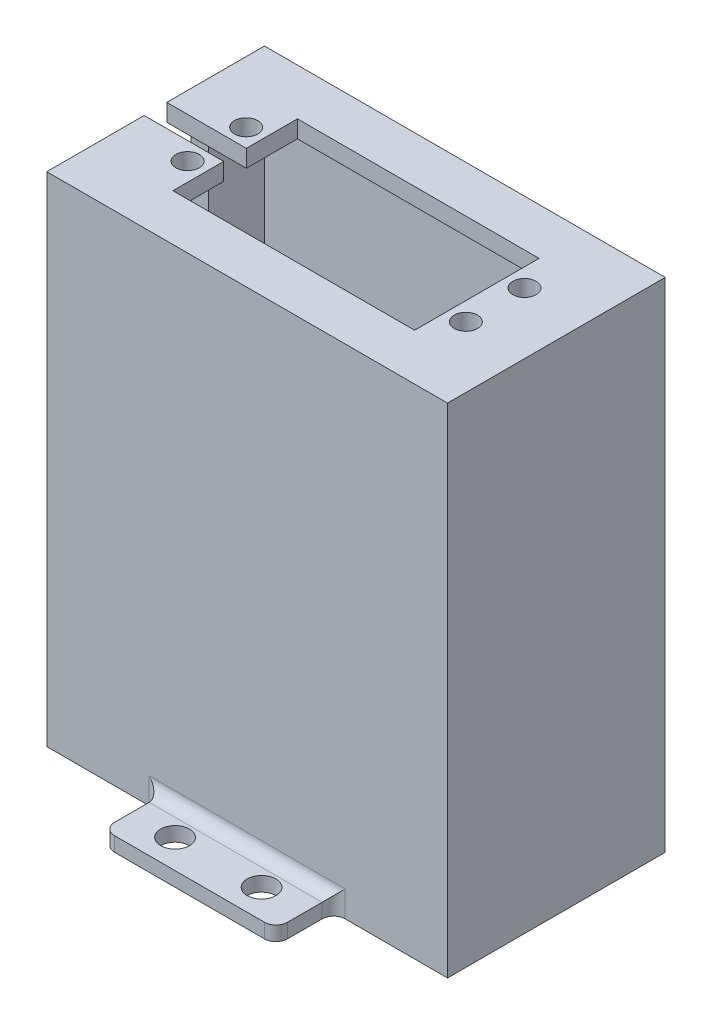
SolidWorks part; units mm, degrees
material "ABS"
ref_plane "Front Plane" through (0, 0, 0) normal (0, 0, 1) x (1, 0, 0)
ref_plane "Top Plane" through (0, 0, 0) normal (0, 1, 0) x (1, 0, 0)
ref_plane "Right Plane" through (0, 0, 0) normal (1, 0, 0) x (0, 0, -1)
sketch "Sketch1" plane through (0, 0, 0) normal (0, 1, 0) x (1, 0, 0)
  line L0 (-303.5027, 0) -> (303.5027, 0) construction
  line L1 (-223.52, -111.125) -> (223.52, -111.125)
  line L2 (-228.6, -106.045) -> (-228.6, 106.045)
  line L3 (-223.52, 111.125) -> (223.52, 111.125)
  line L4 (228.6, -106.045) -> (228.6, 106.045)
  line L5 (-228.6, -111.125) -> (228.6, 111.125) construction
  line L6 (-228.6, 111.125) -> (228.6, -111.125) construction
  line L7 (-303.5027, 36.5125) -> (303.5027, 36.5125) construction
  line L8 (-303.5027, -36.5125) -> (303.5027, -36.5125) construction
  line L9 (127, 111.125) -> (127, -111.125) construction
  line L10 (-142.24, 111.125) -> (-142.24, -111.125) construction
  arc A0 (223.52, 111.125) -> (228.6, 106.045) centre (223.52, 106.045) cw
  arc A1 (223.52, -111.125) -> (228.6, -106.045) centre (223.52, -106.045) ccw
  arc A2 (-223.52, -111.125) -> (-228.6, -106.045) centre (-223.52, -106.045) cw
  arc A3 (-228.6, 106.045) -> (-223.52, 111.125) centre (-223.52, 106.045) cw
  circle A4 centre (127, 36.5125) radius 2.54
  circle A5 centre (127, -36.5125) radius 2.54
  circle A6 centre (-142.24, 36.5125) radius 2.54
  circle A7 centre (-142.24, -36.5125) radius 2.54
  circle A8 centre (209.55, 0) radius 6.35
  point P0 (0, 0)
  point P20 (0, 0)
  point P37 (228.6, 0)
  dimension "D3" = 5.08
  dimension "D7" = 5.08
  dimension "D9" = 12.7
  dimension "D1" = 222.25
  dimension "D2" = 457.2
  dimension "D6" = 269.24
  dimension "D8" = 101.6
  dimension "D10" = 19.05
  dimension "D4" = 36.5125
  dimension "D5" = 36.5125
extrude "mainbaseplate" add sketch "Sketch1" along normal blind 3
sketch "Sketch2" plane through (0, 0, 0) normal (0, -1, 0) x (1, 0, 0)
  circle A0 centre (-142.24, 36.5125) radius 2.54 construction
  circle A1 centre (-142.24, -36.5125) radius 2.54 construction
  circle A2 centre (127, -36.5125) radius 2.54 construction
  circle A3 centre (127, 36.5125) radius 2.54 construction
  circle A4 centre (-142.24, 36.5125) radius 2.54
  circle A5 centre (-142.24, -36.5125) radius 2.54
  circle A6 centre (127, -36.5125) radius 2.54
  circle A7 centre (127, 36.5125) radius 2.54
  circle A8 centre (127, 36.5125) radius 6.096
  circle A9 centre (127, -36.5125) radius 6.096
  circle A10 centre (-142.24, -36.5125) radius 6.096
  circle A11 centre (-142.24, 36.5125) radius 6.096
  dimension "D1" = 12.192
extrude "BaseBoss-Extrude2" [suppressed] add sketch "Sketch2" along normal blind 10.16
sketch "Sketch3" plane through (0, 0, 0) normal (0, -1, 0) x (1, 0, 0)
  line L0 (-228.6, 0) -> (228.6, 0) construction
  line L1 (-228.6, -106.045) -> (-228.6, 106.045) construction
  line L2 (228.6, 106.045) -> (228.6, -106.045) construction
  line L3 (-228.6, 28.4) -> (-73.2, 28.4)
  line L4 (-228.6, -25.4) -> (-76.2, -25.4)
  line L6 (-228.6, 25.4) -> (-76.2, 25.4)
  line L7 (-76.2, -25.4) -> (-76.2, 25.4)
  line L8 (-228.6, -25.4) -> (-76.2, 25.4) construction
  line L9 (-228.6, 25.4) -> (-76.2, -25.4) construction
  line L10 (-73.2, -28.4) -> (-73.2, 28.4)
  line L11 (-228.6, -28.4) -> (-73.2, -28.4)
  line L12 (-228.6, 28.4) -> (-228.6, 25.4)
  line L13 (-228.6, -25.4) -> (-228.6, -28.4)
  point P6 (-152.4, 0)
  dimension "D1" = 50.8
  dimension "D2" = 152.4
  dimension "D3" = 76.2
  dimension "D4" = 3
extrude "Drive BatteryBoss-Extrude1" [suppressed] add sketch "Sketch3" along normal blind 28.575
sketch "Sketch4" [suppressed] plane through (0, -28.575, 0) normal (0, -1, 0) x (1, 0, 0)
  line L1 (-228.6, 28.4) -> (-73.2, 28.4)
  line L2 (-228.6, 28.4) -> (-228.6, -28.4)
  line L3 (-228.6, -28.4) -> (-73.2, -28.4)
  line L4 (-73.2, 28.4) -> (-73.2, -28.4)
extrude "drive Battery CapBoss-Extrude2" [suppressed] add sketch "Sketch4" along normal blind 3
sketch "Sketch5" [suppressed] plane through (0, -31.575, 0) normal (0, -1, 0) x (1, 0, 0)
  line L0 (-98.6, -28.4) -> (-73.2, -3)
  line L1 (-228.6, -28.4) -> (-73.2, -28.4) construction
  line L2 (-73.2, -28.4) -> (-73.2, 28.4) construction
  line L3 (-73.2, -3) -> (-52.1474, -3)
  line L4 (-52.1474, -3) -> (-52.1474, -43.6373)
  line L5 (-52.1474, -43.6373) -> (-98.6, -43.6373)
  line L6 (-98.6, -43.6373) -> (-98.6, -28.4)
  dimension "D1" = 25.4
  dimension "D2" = 25.4
  dimension "D3" = 21.0526
  dimension "D4" = 15.2373
extrude "Drive batterycutoutCut-Extrude1" [suppressed] cut sketch "Sketch5" against normal up to surface (31.575 mm away)
sketch "Sketch6" plane through (0, 3, 0) normal (0, 1, 0) x (1, 0, 0)
  line L0 (-228.6, 0) -> (228.6, 0) construction
  line L1 (-228.6, 106.045) -> (-228.6, -106.045) construction
  line L2 (228.6, -106.045) -> (228.6, 106.045) construction
  line L3 (-63.5, -41.1) -> (66.5, -41.1)
  line L4 (-63.5, -38.1) -> (63.5, -38.1)
  line L6 (-63.5, 38.1) -> (63.5, 38.1)
  line L7 (63.5, -38.1) -> (63.5, 38.1)
  line L8 (-63.5, -38.1) -> (63.5, 38.1) construction
  line L9 (-63.5, 38.1) -> (63.5, -38.1) construction
  line L10 (66.5, -41.1) -> (66.5, 41.1)
  line L11 (-63.5, 41.1) -> (66.5, 41.1)
  line L12 (-63.5, -41.1) -> (-63.5, -38.1)
  line L13 (-63.5, 38.1) -> (-63.5, 41.1)
  point P6 (0, 0)
  dimension "D1" = 127
  dimension "D2" = 76.2
  dimension "D4" = 63.5
  dimension "D3" = 3
extrude "PiBatteryBoxBoss-Extrude3" [suppressed] add sketch "Sketch6" along normal blind 25.4
sketch "Sketch7" [suppressed] plane through (0, 28.4, 0) normal (0, 1, 0) x (1, 0, 0)
  line L1 (66.5, 41.1) -> (-63.5, 41.1)
  line L2 (66.5, 41.1) -> (66.5, -41.1)
  line L3 (66.5, -41.1) -> (-63.5, -41.1)
  line L4 (-63.5, 41.1) -> (-63.5, -41.1)
extrude "PibatterytopBoss-Extrude4" [suppressed] add sketch "Sketch7" along normal blind 3
sketch "Sketch8" [suppressed] plane through (66.5, 0, 0) normal (1, 0, 0) x (0, 0, -1)
  line L0 (-38.1, 28.4) -> (38.1, 3) construction
  line L1 (38.1, 28.4) -> (-38.1, 28.4) construction
  line L2 (-31.75, 3) -> (31.75, 3)
  line L3 (-31.75, 3) -> (-31.75, 28.4)
  line L4 (-31.75, 28.4) -> (31.75, 28.4)
  line L5 (31.75, 3) -> (31.75, 28.4)
  line L6 (-31.75, 3) -> (31.75, 28.4) construction
  line L7 (-31.75, 28.4) -> (31.75, 3) construction
  point P2 (0, 15.7)
  dimension "D1" = 31.75
extrude "pibatterywiresCut-Extrude2" [suppressed] cut sketch "Sketch8" against normal blind 13.16
sketch "Sketch9" [suppressed] plane through (0, 31.4, 0) normal (0, 1, 0) x (1, 0, 0)
  line L0 (-63.5, 41.1) -> (66.5, -41.1) construction
  line L1 (-63.5, 0) -> (66.5, 0) construction
  line L2 (-5.08, -24.489) -> (52.92, -24.489) construction
  line L3 (-5.08, -24.489) -> (-5.08, 24.511) construction
  line L4 (-5.08, 24.511) -> (52.92, 24.511) construction
  line L5 (52.92, -24.489) -> (52.92, 24.511) construction
  line L6 (-5.08, -24.489) -> (52.92, 24.511) construction
  line L7 (-5.08, 24.511) -> (52.92, -24.489) construction
  line L8 (49.11, 20.701) -> (56.73, 20.701)
  line L9 (49.11, 20.701) -> (49.11, 28.321)
  line L10 (49.11, 28.321) -> (56.73, 28.321)
  line L11 (56.73, 20.701) -> (56.73, 28.321)
  line L12 (49.11, 20.701) -> (56.73, 28.321) construction
  line L13 (49.11, 28.321) -> (56.73, 20.701) construction
  line L14 (49.11, -28.299) -> (56.73, -28.299)
  line L16 (49.11, -20.679) -> (56.73, -20.679)
  line L18 (49.11, -28.299) -> (56.73, -20.679) construction
  line L19 (49.11, -20.679) -> (56.73, -28.299) construction
  line L20 (-8.89, 20.701) -> (-1.27, 20.701)
  line L21 (-8.89, 20.701) -> (-8.89, 28.321)
  line L22 (-8.89, 28.321) -> (-1.27, 28.321)
  line L23 (-1.27, 20.701) -> (-1.27, 28.321)
  line L24 (-8.89, 20.701) -> (-1.27, 28.321) construction
  line L25 (-8.89, 28.321) -> (-1.27, 20.701) construction
  line L26 (-8.89, -27.7078) -> (-1.27, -27.7078)
  line L27 (-8.89, -27.7078) -> (-8.89, -21.2702)
  line L28 (-8.89, -21.2702) -> (-1.27, -21.2702)
  line L29 (-1.27, -27.7078) -> (-1.27, -21.2702)
  line L30 (-8.89, -27.7078) -> (-1.27, -21.2702) construction
  line L31 (-8.89, -21.2702) -> (-1.27, -27.7078) construction
  line L32 (-63.5, 41.1) -> (-63.5, -41.1) construction
  line L33 (66.5, -41.1) -> (66.5, 41.1) construction
  line L34 (56.73, -20.679) -> (56.73, -28.299)
  line L35 (49.11, -20.679) -> (49.11, -28.299)
  circle A0 centre (52.92, 24.511) radius 1.35
  circle A1 centre (-5.08, 24.511) radius 1.35
  circle A2 centre (-5.08, -24.489) radius 1.35
  circle A3 centre (52.92, -24.489) radius 1.35
  point P4 (-8.057, 0)
  dimension "D3" = 2.7
  dimension "D4" = 7.62
  dimension "D1" = 58
  dimension "D2" = 49
  dimension "D5" = 7.62
  dimension "D6" = 7.62
  dimension "D7" = 7.62
  dimension "D8" = 7.62
  dimension "D9" = 7.62
  dimension "D10" = 58.42
  dimension "D11" = 24.511
  dimension "D12" = 7.62
extrude "PiBoardBoss-Extrude5" [suppressed] add sketch "Sketch9" along normal blind 3
sketch "Sketch10" plane through (0, 3, 0) normal (0, 1, 0) x (1, 0, 0)
  line L0 (228.6, 0) -> (-228.6, 0) construction
  line L1 (228.6, -106.045) -> (228.6, 106.045) construction
  line L2 (-228.6, 106.045) -> (-228.6, -106.045) construction
  line L3 (104.95, 18.875) -> (174.45, 18.875)
  line L4 (107.95, -15.875) -> (171.45, -15.875)
  line L5 (107.95, -15.875) -> (107.95, -6.175)
  line L6 (107.95, 15.875) -> (171.45, 15.875)
  line L7 (171.45, -15.875) -> (171.45, 15.875)
  line L8 (107.95, -15.875) -> (171.45, 15.875) construction
  line L9 (107.95, 15.875) -> (171.45, -15.875) construction
  line L10 (174.45, -18.875) -> (174.45, 18.875)
  line L11 (104.95, -18.875) -> (174.45, -18.875)
  line L12 (104.95, -18.875) -> (104.95, -6.175)
  line L13 (104.95, 6.175) -> (107.95, 6.175)
  line L14 (104.95, -6.175) -> (107.95, -6.175)
  line L15 (104.95, 6.175) -> (104.95, 18.875)
  line L16 (104.95, -18.875) -> (104.95, 18.875) construction
  line L17 (107.95, 6.175) -> (107.95, 15.875)
  line L18 (107.95, -15.875) -> (107.95, 15.875) construction
  point P6 (139.7, 0)
  dimension "D1" = 31.75
  dimension "D2" = 63.5
  dimension "D3" = 139.7
  dimension "D5" = 12.7
  dimension "D6" = 12.7
  dimension "D4" = 3
extrude "PanTilt-Extrude6" add sketch "Sketch10" along normal blind 83.34
sketch "Sketch11" plane through (0, 86.34, 0) normal (0, 1, 0) x (1, 0, 0)
  line L1 (104.95, 18.875) -> (174.45, 18.875)
  line L2 (104.95, 18.875) -> (104.95, -18.875)
  line L3 (104.95, -18.875) -> (174.45, -18.875)
  line L4 (174.45, 18.875) -> (174.45, -18.875)
extrude "Boss-Extrude7" add sketch "Sketch11" along normal blind 3
sketch "Sketch12" plane through (0, 89.34, 0) normal (0, 1, 0) x (1, 0, 0)
  line L0 (104.95, 0) -> (174.45, 0) construction
  line L1 (104.95, 18.875) -> (104.95, -18.875) construction
  line L2 (174.45, -18.875) -> (174.45, 18.875) construction
  line L3 (118.745, 1.9377) -> (104.95, 1.9377)
  line L4 (118.745, -10.795) -> (160.655, -10.795)
  line L5 (118.745, -10.795) -> (118.745, -1.9901)
  line L6 (118.745, 10.795) -> (160.655, 10.795)
  line L7 (160.655, -10.795) -> (160.655, 10.795)
  line L8 (118.745, -10.795) -> (160.655, 10.795) construction
  line L9 (118.745, 10.795) -> (160.655, -10.795) construction
  line L10 (115.57, -5.08) -> (163.83, -5.08) construction
  line L11 (115.57, -5.08) -> (115.57, 5.08) construction
  line L12 (115.57, 5.08) -> (163.83, 5.08) construction
  line L13 (163.83, -5.08) -> (163.83, 5.08) construction
  line L14 (115.57, -5.08) -> (163.83, 5.08) construction
  line L15 (115.57, 5.08) -> (163.83, -5.08) construction
  line L16 (118.745, -1.9901) -> (104.95, -1.9901)
  line L17 (118.745, 1.9377) -> (118.745, 10.795)
  line L18 (104.95, 1.9377) -> (95.8416, 0)
  line L19 (95.8416, 0) -> (104.95, -1.9901)
  circle A0 centre (163.83, 5.08) radius 2.0193
  circle A1 centre (163.83, -5.08) radius 2.0193
  circle A2 centre (115.57, 5.08) radius 2.0193
  circle A3 centre (115.57, -5.08) radius 2.0193
  point P6 (139.7, 0)
  point P11 (139.7, 0)
  dimension "D5" = 4.0386
  dimension "D1" = 21.59
  dimension "D2" = 41.91
  dimension "D3" = 48.26
  dimension "D4" = 10.16
  dimension "D6" = 1.9377
  dimension "D7" = 1.9901
extrude "Cut-Extrude3" cut sketch "Sketch12" against normal up to surface (86.34 mm away) up to face at (209.55, 3, 6.35)
sketch "Sketch13" plane through (0, 3, 0) normal (0, 1, 0) x (1, 0, 0)
  line L0 (228.6, 0) -> (-228.6, 0) construction
  line L1 (228.6, -106.045) -> (228.6, 106.045) construction
  line L2 (-228.6, 106.045) -> (-228.6, -106.045) construction
  line L3 (198.12, 0) -> (198.12, 25.4)
  line L4 (198.12, 25.4) -> (172.72, 69.3941)
  line L5 (172.72, 69.3941) -> (136.799, 105.3151)
  line L6 (198.12, 25.4) -> (198.12, 129.9736) construction
  line L7 (172.72, 69.3941) -> (172.72, 97.5573) construction
  line L8 (136.799, 105.3151) -> (-185.781, 105.3151)
  line L9 (-185.781, 105.3151) -> (-221.702, 69.3941)
  line L10 (-221.702, 69.3941) -> (-221.702, 0)
  line L11 (-185.781, 105.3151) -> (-290.6809, 105.3151) construction
  line L12 (195.12, 0) -> (195.12, 24.5962)
  line L13 (195.12, 24.5962) -> (170.3194, 67.552)
  line L14 (170.3194, 67.552) -> (135.5563, 102.3151)
  line L15 (135.5563, 102.3151) -> (-184.5384, 102.3151)
  line L16 (-184.5384, 102.3151) -> (-218.702, 68.1514)
  line L17 (-218.702, 68.1514) -> (-218.702, 0)
  line L18 (172.72, -69.3941) -> (172.72, -97.5573) construction
  line L19 (198.12, -25.4) -> (198.12, -129.9736) construction
  line L20 (-218.702, -68.1514) -> (-218.702, 0)
  line L21 (-184.5384, -102.3151) -> (-218.702, -68.1514)
  line L22 (135.5563, -102.3151) -> (-184.5384, -102.3151)
  line L23 (170.3194, -67.552) -> (135.5563, -102.3151)
  line L24 (195.12, -24.5962) -> (170.3194, -67.552)
  line L25 (195.12, 0) -> (195.12, -24.5962)
  line L26 (-221.702, -69.3941) -> (-221.702, 0)
  line L27 (-185.781, -105.3151) -> (-221.702, -69.3941)
  line L28 (136.799, -105.3151) -> (-185.781, -105.3151)
  line L29 (172.72, -69.3941) -> (136.799, -105.3151)
  line L30 (198.12, -25.4) -> (172.72, -69.3941)
  line L31 (198.12, 0) -> (198.12, -25.4)
  dimension "D1" = 30.48
  dimension "D2" = 25.4
  dimension "D3" = 30
  dimension "D4" = 50.8
  dimension "D5" = 45
  dimension "D6" = 50.8
  dimension "D7" = 322.58
  dimension "D8" = 50.8
  dimension "D9" = 45
  dimension "D10" = 3
extrude "Bottom Shell WallsBoss-Extrude8" [suppressed] add sketch "Sketch13" along normal blind 68.58
sketch "Sketch14" [suppressed] plane through (121.057, 0, -121.057) normal (0.7071, 0, -0.7071) x (-0.7071, 0, -0.7071)
  line L0 (-47.6625, 71.58) -> (-47.6625, 3) construction
  line L1 (-73.0625, 71.58) -> (-22.2625, 71.58) construction
  line L2 (-73.0625, 3) -> (-22.2625, 3) construction
  line L3 (-47.6625, 37.29) -> (-25.0131, 37.29) construction
  circle A0 centre (-47.6625, 64.722) radius 1.3526
  circle A1 centre (-47.6625, 9.858) radius 1.3526
  circle A2 centre (-29.8825, 37.29) radius 4.7625
  point P10 (-47.6625, 37.29)
  dimension "D1" = 2.7051
  dimension "D4" = 9.525
  dimension "D2" = 54.864
  dimension "D3" = 27.432
  dimension "D5" = 17.78
extrude "Sharp1Cut-Extrude4" [suppressed] cut sketch "Sketch14" against normal blind 12.7
sketch "Sketch15" [suppressed] plane through (159.5885, 0, -92.1385) normal (0.866, 0, -0.5) x (-0.5, 0, -0.866)
  line L0 (-51.663, 71.58) -> (-51.663, 3) construction
  line L1 (-77.063, 71.58) -> (-26.263, 71.58) construction
  line L2 (-77.063, 3) -> (-26.263, 3) construction
  line L3 (-51.663, 37.29) -> (-29.7061, 37.29) construction
  circle A0 centre (-51.663, 64.722) radius 1.3526
  circle A1 centre (-51.663, 9.858) radius 1.3526
  circle A2 centre (-33.883, 37.29) radius 4.7625
  point P10 (-51.663, 37.29)
  dimension "D1" = 2.7051
  dimension "D4" = 9.525
  dimension "D2" = 27.432
  dimension "D3" = 54.864
  dimension "D5" = 17.78
extrude "Sharp2Cut-Extrude5" [suppressed] cut sketch "Sketch15" against normal blind 7.62
sketch "Sketch16" [suppressed] plane through (198.12, 0, 0) normal (1, 0, 0) x (0, 0, -1)
  line L0 (0, 71.58) -> (0, 3) construction
  line L1 (-25.4, 71.58) -> (25.4, 71.58) construction
  line L2 (-25.4, 3) -> (25.4, 3) construction
  line L3 (0, 37.29) -> (21.2381, 37.29) construction
  circle A0 centre (0, 64.722) radius 1.3526
  circle A1 centre (0, 9.858) radius 1.3525
  circle A2 centre (17.78, 37.29) radius 4.7625
  dimension "D1" = 2.7051
  dimension "D4" = 9.525
  dimension "D2" = 27.432
  dimension "D3" = 54.864
  dimension "D5" = 17.78
extrude "Sharp3Cut-Extrude6" [suppressed] cut sketch "Sketch16" against normal blind 7.62
sketch "Sketch17" [suppressed] plane through (159.5885, 0, 92.1385) normal (0.866, 0, 0.5) x (0.5, 0, -0.866)
  line L0 (51.663, 71.58) -> (51.663, 3) construction
  line L1 (26.263, 71.58) -> (77.063, 71.58) construction
  line L2 (26.263, 3) -> (77.063, 3) construction
  line L3 (51.663, 37.29) -> (70.4023, 37.29) construction
  circle A0 centre (51.663, 64.722) radius 1.3526
  circle A1 centre (51.663, 9.858) radius 1.3526
  circle A2 centre (69.443, 37.29) radius 4.7625
  dimension "D1" = 2.7051
  dimension "D2" = 2.7051
  dimension "D3" = 9.525
  dimension "D4" = 17.78
  dimension "D5" = 27.432
  dimension "D6" = 54.864
extrude "SharpCut-Extrude7" [suppressed] cut sketch "Sketch17" against normal blind 7.62
sketch "Sketch18" [suppressed] plane through (121.057, 0, 121.057) normal (0.7071, 0, 0.7071) x (0.7071, 0, -0.7071)
  line L0 (47.6625, 71.58) -> (47.6625, 3) construction
  line L1 (22.2625, 71.58) -> (73.0625, 71.58) construction
  line L2 (22.2625, 3) -> (73.0625, 3) construction
  line L3 (25.604, 37.29) -> (69.7209, 37.29) construction
  circle A0 centre (47.6625, 64.722) radius 1.3526
  circle A1 centre (47.6625, 9.858) radius 1.3526
  circle A2 centre (65.4425, 37.29) radius 4.7625
  point P13 (47.6625, 37.29)
  dimension "D1" = 9.525
  dimension "D3" = 2.7051
  dimension "D4" = 2.7051
  dimension "D2" = 17.78
  dimension "D5" = 27.432
  dimension "D6" = 54.864
extrude "SharpCut-Extrude8" [suppressed] cut sketch "Sketch18" against normal blind 7.62
sketch "Sketch19" [suppressed] plane through (0, 71.58, 0) normal (0, 1, 0) x (1, 0, 0)
  line L0 (-223.52, -111.125) -> (223.52, -111.125) construction
  line L1 (228.6, -106.045) -> (228.6, 106.045) construction
  line L2 (223.52, 111.125) -> (-223.52, 111.125) construction
  line L3 (104.95, -111.125) -> (223.52, -111.125)
  line L4 (228.6, -106.045) -> (228.6, 106.045)
  line L5 (223.52, 111.125) -> (104.95, 111.125)
  line L6 (104.95, 111.125) -> (104.95, -111.125)
  arc A0 (223.52, -111.125) -> (228.6, -106.045) centre (223.52, -106.045) ccw construction
  arc A1 (228.6, 106.045) -> (223.52, 111.125) centre (223.52, 106.045) ccw construction
  arc A2 (223.52, -111.125) -> (228.6, -106.045) centre (223.52, -106.045) ccw
  arc A3 (228.6, 106.045) -> (223.52, 111.125) centre (223.52, 106.045) ccw
extrude "TopSensorplateBoss-Extrude8" [suppressed] add sketch "Sketch19" along normal blind 3
sketch "Sketch21" [suppressed] plane through (0, 74.58, 0) normal (0, 1, 0) x (1, 0, 0)
  line L0 (104.95, -18.875) -> (174.45, -18.875) construction
  line L1 (174.45, -18.875) -> (174.45, 18.875) construction
  line L2 (174.45, 18.875) -> (104.95, 18.875) construction
  line L3 (104.95, -18.875) -> (164.29, -18.875)
  line L4 (174.45, -8.715) -> (174.45, 8.715)
  line L5 (164.29, 18.875) -> (104.95, 18.875)
  line L6 (104.95, 18.875) -> (84.8462, 2.2825)
  line L7 (84.8462, 2.2825) -> (104.95, -18.875)
  arc A0 (164.29, -18.875) -> (174.45, -8.715) centre (164.29, -8.715) ccw
  arc A1 (174.45, 8.715) -> (164.29, 18.875) centre (164.29, 8.715) ccw
  circle A2 centre (127, -36.5125) radius 6.096 construction
  circle A3 centre (127, 36.5125) radius 6.096 construction
  circle A4 centre (127, -36.5125) radius 6.096
  circle A5 centre (127, 36.5125) radius 6.096
  dimension "D1" = 10.16
extrude "topsensorplateCut-Extrude4" [suppressed] cut sketch "Sketch21" against normal blind 8.08
sketch "Sketch22" [suppressed] plane through (0, 0, 0) normal (0, -1, 0) x (1, 0, 0)
  line L0 (228.6, 0) -> (-228.6, 0) construction
  line L1 (228.6, 106.045) -> (228.6, -106.045) construction
  line L2 (-228.6, 28.4) -> (-228.6, -28.4) construction
  line L3 (220.98, 0) -> (220.98, 76.2)
  line L4 (220.98, 76.2) -> (193.675, 103.505)
  line L5 (193.675, 103.505) -> (-25.4, 103.505)
  line L6 (-223.52, 111.125) -> (223.52, 111.125) construction
  line L7 (217.98, 0) -> (217.98, 74.9574)
  line L8 (217.98, 74.9574) -> (192.4324, 100.505)
  line L9 (192.4324, 100.505) -> (-25.4, 100.505)
  line L10 (-25.4, 103.505) -> (-25.4, 100.505)
  line L11 (217.98, 0) -> (217.98, -74.9574)
  line L12 (220.98, 0) -> (220.98, -76.2)
  line L13 (-25.4, -103.505) -> (-25.4, -100.505)
  line L14 (192.4324, -100.505) -> (-25.4, -100.505)
  line L15 (217.98, -74.9574) -> (192.4324, -100.505)
  line L16 (193.675, -103.505) -> (-25.4, -103.505)
  line L17 (220.98, -76.2) -> (193.675, -103.505)
  line L18 (-220.98, 28.4) -> (-220.98, 76.2)
  line L19 (-73.2, 28.4) -> (-228.6, 28.4) construction
  line L20 (-220.98, 76.2) -> (-193.548, 103.505)
  line L21 (-193.548, 103.505) -> (-127, 103.505)
  line L22 (-228.6, 28.4) -> (-228.6, 106.045) construction
  line L23 (-217.98, 28.4) -> (-217.98, 74.9533)
  line L24 (-217.98, 74.9533) -> (-192.3094, 100.505)
  line L25 (-192.3094, 100.505) -> (-127, 100.505)
  line L26 (-127, 103.505) -> (-127, 100.505)
  line L27 (-220.98, 28.4) -> (-217.98, 28.4)
  line L28 (-127, -103.505) -> (-127, -100.505)
  line L29 (-192.3094, -100.505) -> (-127, -100.505)
  line L30 (-217.98, -74.9533) -> (-192.3094, -100.505)
  line L31 (-217.98, -28.4) -> (-217.98, -74.9533)
  line L32 (-193.548, -103.505) -> (-127, -103.505)
  line L33 (-220.98, -76.2) -> (-193.548, -103.505)
  line L34 (-220.98, -28.4) -> (-220.98, -76.2)
  line L35 (-220.98, -28.4) -> (-217.98, -28.4)
  dimension "D1" = 7.62
  dimension "D2" = 7.62
  dimension "D3" = 76.2
  dimension "D4" = 34.925
  dimension "D5" = 254
  dimension "D7" = 7.62
  dimension "D8" = 76.2
  dimension "D9" = 7.62
  dimension "D10" = 101.6
  dimension "D11" = 35.052
  dimension "D6" = 3
  dimension "D12" = 3
extrude "frontrockerpanBoss-Extrude9" [suppressed] add sketch "Sketch22" along normal blind 45.72
sketch "Sketch23" [suppressed] plane through (0, 0, -103.505) normal (0, 0, -1) x (-1, 0, 0)
  line L0 (25.4, 0) -> (-193.675, 0) construction
  line L2 (-223.1134, -81.0052) -> (22.7571, -81.0052) construction
  line L3 (22.7571, -81.0052) -> (254.0819, -81.0052) construction
  circle A1 centre (-127, -81.0052) radius 63.5
  circle A2 centre (152.4, -81.0052) radius 63.5
  dimension "D1" = 81.0052
  dimension "D4" = 127
  dimension "D2" = 22.7571
  dimension "D3" = 223.1134
  dimension "D5" = 127
  dimension "D6" = 279.4
extrude "TireCut-Extrude5" [suppressed] cut sketch "Sketch23" against normal blind 25.4
sketch "Sketch24" [suppressed] plane through (-221.702, 0, 0) normal (-1, 0, 0) x (0, 0, 1)
  line L0 (-69.3941, 71.58) -> (69.3941, 3) construction
  circle A0 centre (0, 37.29) radius 10.9855
  dimension "D1" = 21.971
extrude "Cut-Extrude6" [suppressed] cut sketch "Sketch24" against normal blind 7.62
sketch "Sketch25" [suppressed] plane through (0, 71.58, 0) normal (0, 1, 0) x (1, 0, 0)
  line L3 (-223.52, -111.125) -> (223.52, -111.125) construction
  line L5 (-228.6, 106.045) -> (-228.6, -106.045) construction
  line L6 (223.52, 111.125) -> (-223.52, 111.125) construction
  line L7 (-223.52, -111.125) -> (-147.32, -111.125)
  line L8 (-228.6, 106.045) -> (-228.6, -106.045)
  line L9 (-147.32, 111.125) -> (-223.52, 111.125)
  line L10 (-147.32, 111.125) -> (-147.32, -111.125)
  arc A2 (-228.6, -106.045) -> (-223.52, -111.125) centre (-223.52, -106.045) ccw construction
  arc A3 (-223.52, 111.125) -> (-228.6, 106.045) centre (-223.52, 106.045) ccw construction
  arc A4 (-228.6, -106.045) -> (-223.52, -111.125) centre (-223.52, -106.045) ccw
  arc A5 (-223.52, 111.125) -> (-228.6, 106.045) centre (-223.52, 106.045) ccw
  dimension "D1" = 147.32
extrude "ReartopdeckBoss-Extrude10" [suppressed] add sketch "Sketch25" along normal blind 3
sketch "Sketch28" [suppressed] plane through (0, 0, 103.505) normal (0, 0, 1) x (1, 0, 0)
  line L0 (-205.194, -45.72) -> (-93.1399, -108.4782)
  line L1 (-93.1399, -108.4782) -> (179.794, -45.72)
  line L2 (74.206, -45.72) -> (-102.0458, -69.7467)
  line L3 (-102.0458, -69.7467) -> (-127, -22.8065)
  arc A0 (-192.3094, -31.6141) -> (-205.194, -45.72) centre (-152.4, -81.0052) ccw construction
  arc A1 (-127, -22.8065) -> (-192.3094, -31.6141) centre (-152.4, -81.0052) ccw construction
  arc A2 (179.794, -45.72) -> (74.206, -45.72) centre (127, -81.0052) ccw construction
  arc A3 (-192.3094, -31.6141) -> (-205.194, -45.72) centre (-152.4, -81.0052) ccw
  arc A4 (-127, -22.8065) -> (-192.3094, -31.6141) centre (-152.4, -81.0052) ccw
  arc A5 (179.794, -45.72) -> (74.206, -45.72) centre (127, -81.0052) ccw
extrude "TireCut-Extrude8" [suppressed] cut sketch "Sketch28" against normal blind 35.56
sketch "Sketch30" [suppressed] plane through (0, 74.58, 0) normal (0, 1, 0) x (1, 0, 0)
  line L0 (-147.32, 0) -> (-228.6, 0) construction
  line L1 (-147.32, -111.125) -> (-147.32, 111.125) construction
  line L2 (-228.6, 106.045) -> (-228.6, -106.045) construction
  circle A0 centre (-166.37, 0) radius 6.35
  dimension "D1" = 12.7
  dimension "D2" = 19.05
extrude "Cut-Extrude10" [suppressed] cut sketch "Sketch30" against normal blind 11.684
sketch "Sketch31" [suppressed] plane through (0, 0, 0) normal (1, 0, 0) x (0, 0, -1)
  line L0 (102.3151, 71.58) -> (102.3151, 3) construction
  line L1 (-102.3151, 71.58) -> (-76.9151, 71.58)
  line L2 (-102.3151, 71.58) -> (-102.3151, 68.58)
  line L3 (-102.3151, 68.58) -> (-76.9151, 68.58)
  line L4 (102.3151, 71.58) -> (102.3151, 68.58)
  line L5 (-76.9151, 71.58) -> (-76.9151, 68.58)
  line L6 (76.9151, 71.58) -> (76.9151, 68.58)
  line L7 (76.9151, 71.58) -> (102.3151, 71.58)
  line L8 (76.9151, 68.58) -> (102.3151, 68.58)
  dimension "D1" = 3
  dimension "D2" = 25.4
  dimension "D3" = 25.4
extrude "Boss-Extrude8" [suppressed] add sketch "Sketch31" along normal blind 134.62 and the other way blind 180.34
sketch "Sketch32" plane through (0, 0, 0) normal (0, -1, 0) x (1, 0, 0)
  line L1 (-362.1056, 298.8668) -> (350.2899, 298.8668)
  line L2 (-362.1056, 298.8668) -> (-362.1056, -225.3293)
  line L3 (-362.1056, -225.3293) -> (350.2899, -225.3293)
  line L4 (350.2899, 298.8668) -> (350.2899, -225.3293)
extrude "Cut-Extrude11" cut sketch "Sketch32" against normal up to surface (3 mm away) up to face at (209.55, 3, 6.35)
sketch "Sketch33" plane through (0, 3, 0) normal (0, -1, 0) x (1, 0, 0)
  line L0 (174.45, 0) -> (90.833, 0) construction
  line L1 (154.7, 28.875) -> (124.7, 28.875)
  line L2 (154.7, 28.875) -> (154.7, -28.875)
  line L3 (154.7, -28.875) -> (124.7, -28.875)
  line L4 (124.7, 28.875) -> (124.7, -28.875)
  line L5 (174.45, 18.875) -> (174.45, -18.875) construction
  line L6 (104.95, 18.875) -> (174.45, 18.875) construction
  line L7 (174.45, -18.875) -> (104.95, -18.875) construction
  line L8 (139.7, -18.875) -> (139.7, 50.2921) construction
  line L9 (147.2, 28.875) -> (147.2, 18.875) construction
  line L10 (154.7, -18.875) -> (124.7, -18.875)
  line L11 (154.7, 18.875) -> (124.7, 18.875)
  circle A0 centre (147.2, 23.875) radius 2.5
  circle A1 centre (132.2, 23.875) radius 2.5
  circle A2 centre (132.2, -23.875) radius 2.5
  circle A3 centre (147.2, -23.875) radius 2.5
  point P9 (139.7, 28.875)
  point P14 (139.7, -28.875)
  point P16 (154.7, 0)
  point P22 (147.2, 23.875)
  line M13 (104.95, -18.875) -> (174.45, -18.875)
  line M15 (174.45, 18.875) -> (104.95, 18.875)
  dimension "D3" = 5
  dimension "D4" = 7.5
  dimension "D1" = 10
  dimension "D2" = 30
extrude "Boss-Extrude9" add sketch "Sketch33" against normal blind 2.5 contours L1 L4 L2 A0 A1 M15 | L4 L3 L2 A2 A3 M13 region at (139.7, 3, 23.875) region at (139.7, 3, -23.875)
fillet "Fillet1" radius 2 10 edges at (154.7, 4.25, 28.875) (124.7, 4.25, 28.875) (124.7, 4.25, 18.875) (154.7, 4.25, 18.875) (139.7, 5.5, 18.875) (124.7, 4.25, -28.875) (124.7, 4.25, -18.875) (154.7, 4.25, -28.875) (154.7, 4.25, -18.875) (139.7, 5.5, -18.875)
